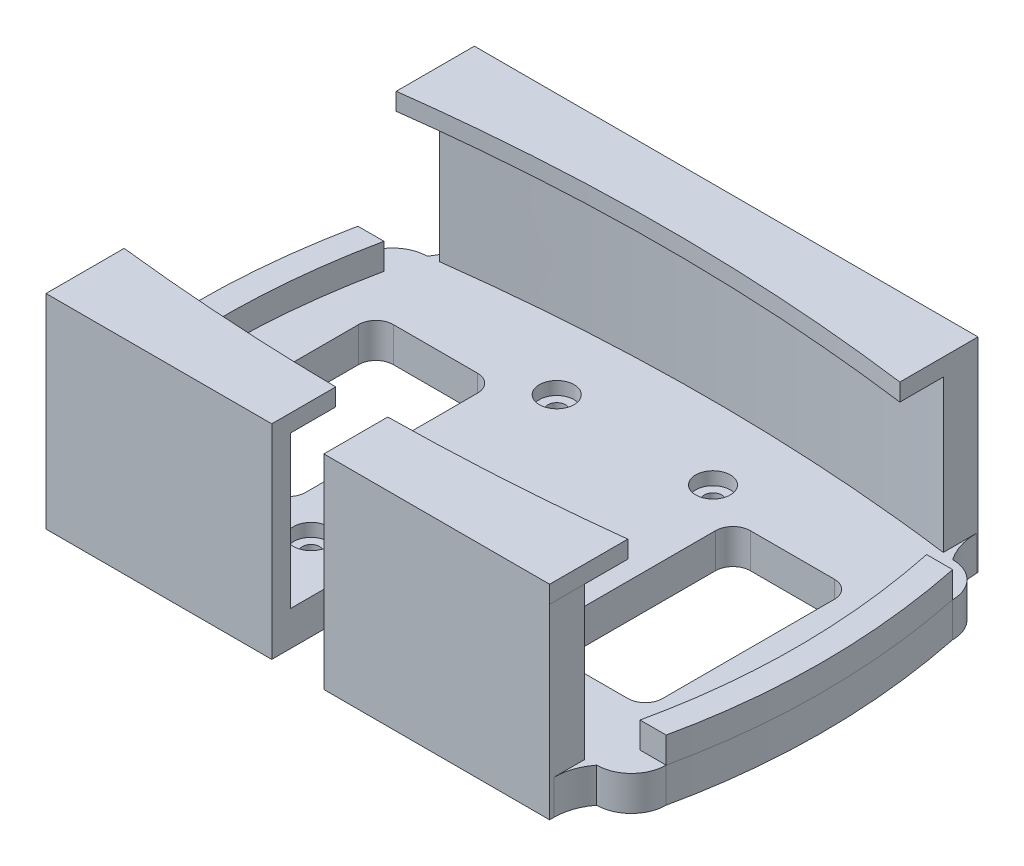
SolidWorks part; units mm, degrees
ref_plane "Front Plane" through (0, 0, 0) normal (0, 0, 1) x (1, 0, 0)
ref_plane "Top Plane" through (0, 0, 0) normal (0, 1, 0) x (1, 0, 0)
ref_plane "Right Plane" through (0, 0, 0) normal (1, 0, 0) x (0, 0, -1)
sketch "Sketch1" plane through (0, 0, 0) normal (0, 1, 0) x (1, 0, 0)
  line L0 (-48.4091, 0) -> (65.8802, 0) construction
  line L5 (-34.25, -20.5) -> (32.7645, 19.6109) construction
  line L6 (-34.25, 20.5) -> (32.7645, -19.6109) construction
  line L7 (0, 33.746) -> (0, -28.2439) construction
  arc A0 (30.25, 20.5) -> (34.25, 16.5) centre (30.25, 16.5) cw
  arc A1 (30.25, -20.5) -> (34.25, -16.5) centre (30.25, -16.5) ccw
  arc A2 (-30.25, -20.5) -> (-34.25, -16.5) centre (-30.25, -16.5) cw
  arc A3 (-34.25, 16.5) -> (-30.25, 20.5) centre (-30.25, 16.5) cw
  spline S0 degree 2 poles (-30.25, 20.5) (0.3443, 24.6056) (30.25, 20.5) knots 0 0 0 0.814994 0.814994 0.814994
  spline S1 degree 2 poles (-34.25, 16.5) (-37.7227, -0.5267) (-34.25, -16.5) knots 0 0 0 0.709822 0.709822 0.709822
  spline S2 degree 2 poles (34.25, 16.5) (37.7227, -0.5267) (34.25, -16.5) knots 0 0 0 0.709822 0.709822 0.709822
  spline S3 degree 2 poles (-30.25, -20.5) (0.3443, -24.6056) (30.25, -20.5) knots 0 0 0 0.814994 0.814994 0.814994
  point P0 (0, 0)
  dimension "D3" = 4
extrude "Boss-Extrude1" add sketch "Sketch1" along normal blind 4
sketch "Sketch2" plane through (0, 4, 0) normal (0, 1, 0) x (1, 0, 0)
  line L0 (-3, 0) -> (-3, -22.5303)
  line L1 (-3, 0) -> (3, 0)
  line L2 (3, 0) -> (3, -22.5348)
  parabola Q0 (-30.25, -20.5) -> (30.25, -20.5) focus (9.4513, 88.1096) apex (18.6658, -21.7802) construction
  parabola Q1 (-30.25, -20.5) -> (30.25, -20.5) focus (9.4513, 88.1096) apex (18.6658, -21.7802) construction
  parabola Q2 (-30.25, -20.5) -> (30.25, -20.5) focus (9.4513, 88.1096) apex (18.6658, -21.7802) construction
  parabola Q3 (-3, -22.5303) -> (3, -22.5348) focus (9.4513, 88.1096) apex (18.6658, -21.7802)
  dimension "D1" = 3
  dimension "D2" = 6
extrude "Cut-Extrude1" cut sketch "Sketch2" against normal blind 17
sketch "Sketch3" plane through (0, 4, 0) normal (0, 1, 0) x (1, 0, 0)
  line L0 (-29, 20.6644) -> (-29, 24.668)
  line L1 (-29, 24.668) -> (29, 24.668)
  line L2 (29, 24.668) -> (29, 20.668)
  parabola Q0 (30.25, 20.5) -> (-30.25, 20.5) focus (9.4513, -88.1096) apex (18.6658, 21.7802) construction
  parabola Q1 (30.25, 20.5) -> (-30.25, 20.5) focus (9.4513, -88.1096) apex (18.6658, 21.7802) construction
  parabola Q2 (30.25, 20.5) -> (-30.25, 20.5) focus (9.4513, -88.1096) apex (18.6658, 21.7802) construction
  parabola Q3 (29, 20.668) -> (-29, 20.6644) focus (9.4513, -88.1096) apex (18.6658, 21.7802)
  point P6 (0, 24.668)
  dimension "D1" = 4
  dimension "D2" = 58
extrude "Boss-Extrude2" add sketch "Sketch3" along normal blind 19.5 separate body
sketch "Sketch4" plane through (0, 4, 0) normal (0, -1, 0) x (1, 0, 0)
  line L3 (-29, -20.6644) -> (-29, -24.668)
  line L4 (-29, -24.668) -> (29, -24.668)
  line L5 (29, -24.668) -> (29, -20.668)
  line L6 (-29, -20.6644) -> (-29, -24.668)
  line L7 (-29, -24.668) -> (29, -24.668)
  line L8 (29, -24.668) -> (29, -20.668)
  parabola Q1 (29, -20.668) -> (-29, -20.6644) focus (9.4513, 88.1096) apex (18.6658, -21.7802)
  parabola Q2 (29, -20.668) -> (-29, -20.6644) focus (9.4513, 88.1096) apex (18.6658, -21.7802)
  dimension "D1" = 0
extrude "Boss-Extrude3" add sketch "Sketch4" along normal up to surface (4 mm away) up to face at (0.25, 0, 3.7556)
sketch "Sketch6" plane through (0, 0, -24.668) normal (0, 0, -1) x (-1, 0, 0)
  line L0 (29, 0) -> (29, 23.5) construction
  line L1 (-29, 23.5) -> (29, 23.5)
  line L2 (-29, 23.5) -> (-29, 21.5)
  line L3 (-29, 21.5) -> (29, 21.5)
  line L4 (29, 23.5) -> (29, 21.5)
  dimension "D1" = 2
extrude "Boss-Extrude4" add sketch "Sketch6" against normal blind 9
sketch "Sketch7" plane through (0, 23.5, 0) normal (0, 1, 0) x (1, 0, 0)
  line L0 (-29, 15.668) -> (29, 15.668)
  spline S0 degree 2 poles (-29, 15.668) (0.2738, 19.4704) (29, 15.668) knots 0 0 0 0.915261 0.915261 0.915261
extrude "Cut-Extrude2" cut sketch "Sketch7" against normal blind 7
fillet "Fillet1" radius 7 2 edges at (-29, 2, -20.6644) (29, 2, -20.668)
ref_plane "Plane1" through (0, 0, 0) normal (0, 0, -1) x (-1, 0, 0)
sketch "Sketch8" plane through (0, 0, 0) normal (0, -1, 0) x (1, 0, 0)
  line L0 (29, 20.668) -> (29, 24.668)
  line L1 (29, 24.668) -> (3, 24.668)
  line L2 (-29, 24.668) -> (-29, 20.2997)
  line L3 (-3, 22.5303) -> (-3, 24.668)
  line L4 (3, 22.5348) -> (3, 24.668)
  line L5 (-3, 24.668) -> (-29, 24.668)
  line L6 (-29, -24.4922) -> (-29, -20.6644) construction
  line L7 (29, -20.668) -> (29, -24.4922) construction
  arc A0 (-30.25, 20.5) -> (-34.25, 16.5) centre (-30.25, 16.5) ccw construction
  parabola Q0 (3, 22.5348) -> (30.25, 20.5) focus (9.4513, -88.1096) apex (18.6658, 21.7802) construction
  parabola Q1 (3, 22.5348) -> (30.25, 20.5) focus (9.4513, -88.1096) apex (18.6658, 21.7802) construction
  parabola Q2 (-30.25, 20.5) -> (-3, 22.5303) focus (9.4513, -88.1096) apex (18.6658, 21.7802) construction
  parabola Q3 (3, 22.5348) -> (30.25, 20.5) focus (9.4513, -88.1096) apex (18.6658, 21.7802)
  parabola Q4 (-30.25, 20.5) -> (-3, 22.5303) focus (9.4513, -88.1096) apex (18.6658, 21.7802)
  spline M4 degree 2 poles (30.25, 20.5) (0.3443, 24.6056) (-30.25, 20.5) knots 0 0 0 0.814994 0.814994 0.814994 only from (30.25, 20.5) to (3, 22.5348)
  spline M8 degree 2 poles (30.25, 20.5) (0.3443, 24.6056) (-30.25, 20.5) knots 0 0 0 0.814994 0.814994 0.814994 only from (-3, 22.5303) to (-30.25, 20.5)
  dimension "D1" = 4
extrude "Boss-Extrude5" add sketch "Sketch8" against normal up to surface (23.5 mm away) contours L3 L5 L2 M8 | L4 L0 L1 M4 region at (17.4387, 0, 23.2094) region at (-17.4335, 0, 23.2031) up to face at (7.25, 23.5, -20.168)
sketch "Sketch9" plane through (0, 0, 24.668) normal (0, 0, 1) x (1, 0, 0)
  line L0 (-3, 23.5) -> (-3, 21.5)
  line L1 (-29, 23.5) -> (-3, 23.5)
  line L2 (-29, 23.5) -> (-29, 21.5)
  line L3 (-29, 21.5) -> (-3, 21.5)
  line L4 (29.0016, 23.5) -> (29.0016, 21.5)
  line L5 (-3, 23.5) -> (-3, 0) construction
  line L6 (3, 23.5) -> (3, 21.5)
  line L7 (3, 23.5) -> (29.0016, 23.5)
  line L8 (3, 21.5) -> (29.0016, 21.5)
  dimension "D1" = 2
extrude "Boss-Extrude6" add sketch "Sketch9" against normal blind 9
sketch "Sketch10" plane through (0, 23.5, 0) normal (0, 1, 0) x (1, 0, 0)
  line L0 (-29, -15.668) -> (29.0016, -15.668)
  spline S0 degree 2 poles (-29, -15.668) (0.2082, -18.978) (29.0016, -15.668) knots 0 0 0 0.914207 0.914207 0.914207
extrude "Cut-Extrude3" cut sketch "Sketch10" against normal blind 10
sketch "Sketch11" plane through (0, 4, 0) normal (0, 1, 0) x (1, 0, 0)
  line L0 (0, 31.4322) -> (0, -43.2633) construction
  line L1 (-21.4932, 14.15) -> (21.931, 14.15) construction
  line L2 (-21.4932, -14.15) -> (21.931, -14.15) construction
  line L3 (3, 0) -> (-3, 0) construction
  circle A0 centre (-9, 14.15) radius 1
  circle A1 centre (-9, -14.15) radius 1
  dimension "D5" = 2
  dimension "D6" = 2
  dimension "D1" = 28.3
  dimension "D2" = 14.15
  dimension "D3" = 9
  dimension "D4" = 9
extrude "Cut-Extrude4" cut sketch "Sketch11" against normal blind 10
sketch "Sketch12" plane through (0, 4, 0) normal (0, 1, 0) x (1, 0, 0)
  circle A0 centre (-9, 14.15) radius 2
  circle A1 centre (-9, -14.15) radius 2
  dimension "D1" = 4
  dimension "D2" = 4
extrude "Cut-Extrude5" cut sketch "Sketch12" against normal blind 1.5
ref_plane "Plane2" through (0, 0, 0) normal (-1, 0, 0) x (0, 0, 1)
mirror "Mirror10" about plane through (0, 0, 0) normal (-1, 0, 0) of "Cut-Extrude5", "Cut-Extrude4"
sketch "Sketch13" plane through (0, 4, 0) normal (0, 1, 0) x (1, 0, 0)
  line L1 (-27.402, -12.0623) -> (-13.7107, -12.0623)
  line L2 (-27.402, -12.0623) -> (-27.402, 11.7331)
  line L3 (-27.402, 11.7331) -> (-13.7107, 11.7331)
  line L4 (-13.7107, -12.0623) -> (-13.7107, 11.7331)
  line L5 (-27.402, -12.0623) -> (-13.7107, 11.7331) construction
  line L6 (-27.402, 11.7331) -> (-13.7107, -12.0623) construction
  point P0 (-20.5563, -0.1646)
extrude "Cut-Extrude6" cut sketch "Sketch13" against normal blind 21.5
fillet "Fillet2" radius 2 4 edges at (-27.402, 2, 12.0623) (-13.7107, 2, 12.0623) (-27.402, 2, -11.7331) (-13.7107, 2, -11.7331)
mirror "Mirror11" about plane through (0, 0, 0) normal (-1, 0, 0) of "Fillet2", "Cut-Extrude6"
fillet "Fillet3" radius 6 2 edges
sketch "Sketch14" plane through (0, 0, 0) normal (0, -1, 0) x (1, 0, 0)
  line L0 (-34.25, 16.5) -> (-31.25, 16.5)
  line L1 (-34.25, -16.5) -> (-31.25, -16.5)
  arc A0 (-34.25, -16.5) -> (-30.25, -20.5) centre (-30.25, -16.5) ccw construction
  arc A1 (-30.25, 20.5) -> (-34.25, 16.5) centre (-30.25, 16.5) ccw construction
  arc A2 (-34.25, -16.5) -> (-30.25, -20.5) centre (-30.25, -16.5) ccw
  arc A3 (-30.25, 20.5) -> (-34.25, 16.5) centre (-30.25, 16.5) ccw
  parabola Q0 (-34.25, -16.5) -> (-34.25, 16.5) focus (2.3313, 6.0747) apex (-35.1248, 11.7553) construction
  parabola Q1 (-34.25, -16.5) -> (-34.25, 16.5) focus (2.3313, 6.0747) apex (-35.1248, 11.7553)
  parabola Q2 (-31.25, -16.5) -> (-31.25, 16.5) focus (5.1301, 4.6494) apex (-32.4997, 9.0341)
  dimension "D1" = 3
  dimension "D2" = 3
extrude "Boss-Extrude7" add sketch "Sketch14" against normal blind 7 contours L1 Q2 L0 region at (-33.9144, 0, 0.0086)
mirror "Mirror12" about plane through (0, 0, 0) normal (-1, 0, 0) of "Boss-Extrude7"
